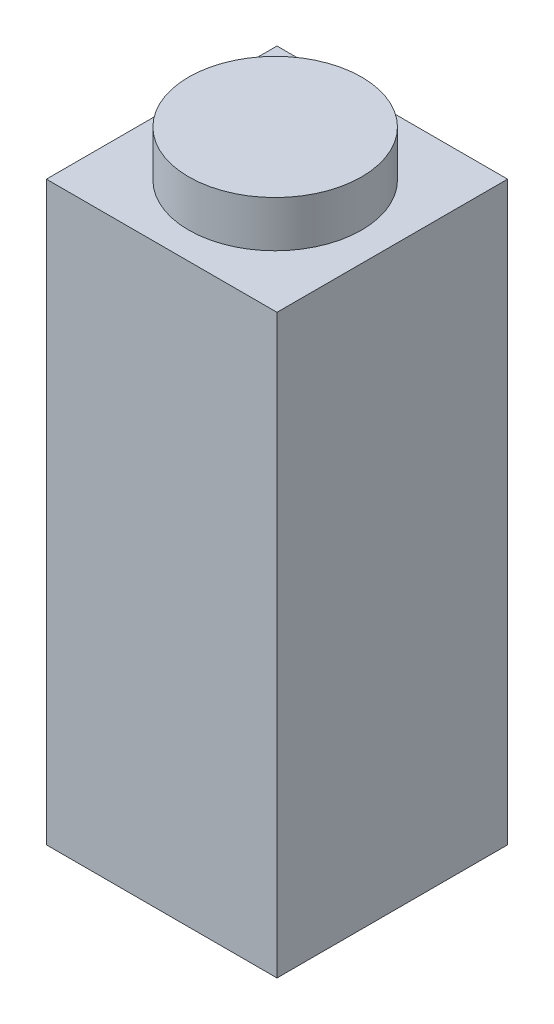
SolidWorks part; units mm, degrees
ref_plane "Front Plane" through (0, 0, 0) normal (0, 0, 1) x (1, 0, 0)
ref_plane "Top Plane" through (0, 0, 0) normal (0, 1, 0) x (1, 0, 0)
ref_plane "Right Plane" through (0, 0, 0) normal (1, 0, 0) x (0, 0, -1)
sketch "Sketch1" plane through (0, 0, 0) normal (0, 1, 0) x (1, 0, 0)
  line L1 (-3, -3) -> (3, -3)
  line L2 (-3, -3) -> (-3, 3)
  line L3 (-3, 3) -> (3, 3)
  line L4 (3, -3) -> (3, 3)
  line L5 (-3, -3) -> (3, 3) construction
  line L6 (-3, 3) -> (3, -3) construction
  point P0 (0, 0)
  dimension "D1" = 6
  dimension "D2" = 6
extrude "Boss-Extrude1" add sketch "Sketch1" along normal blind 15
sketch "Sketch2" plane through (0, 0, 0) normal (0, -1, 0) x (1, 0, 0)
  circle A0 centre (0, 0) radius 1
  dimension "D1" = 2
extrude "Cut-Extrude1" cut sketch "Sketch2" against normal blind 0.5
sketch "Sketch4" plane through (0, 15, 0) normal (0, 1, 0) x (1, 0, 0)
  circle A0 centre (0, -0.0477) radius 2.25
  dimension "D1" = 4.5
extrude "Boss-Extrude2" add sketch "Sketch4" along normal blind 1.2
